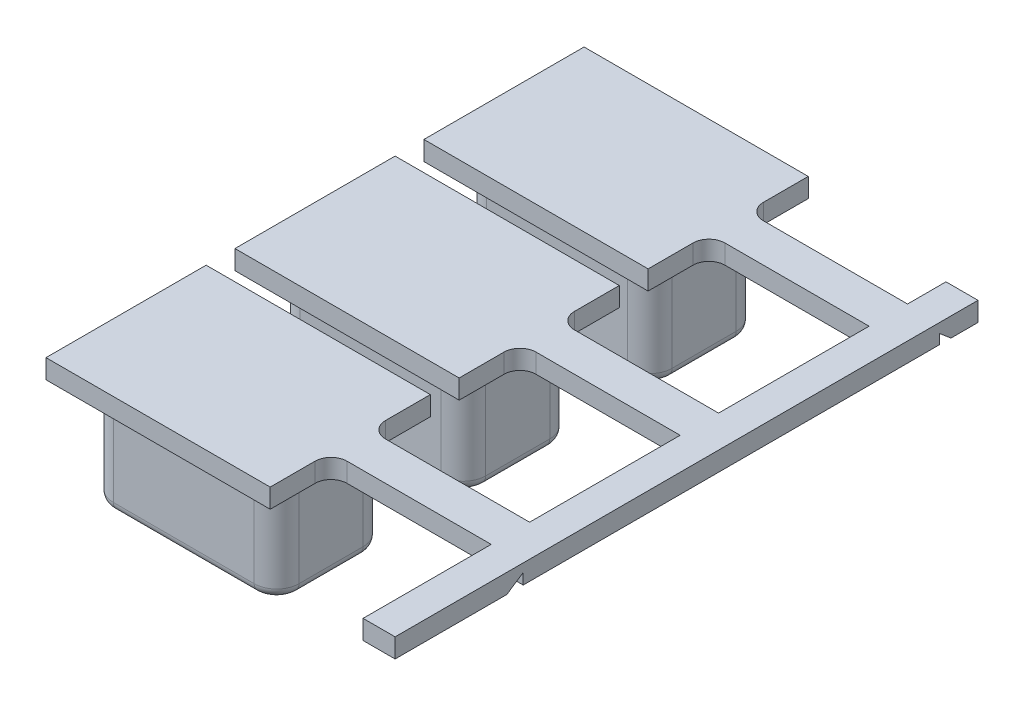
SolidWorks part; units mm, degrees
ref_plane "前视基准面" through (0, 0, 0) normal (0, 0, 1) x (1, 0, 0)
ref_plane "上视基准面" through (0, 0, 0) normal (0, 1, 0) x (1, 0, 0)
ref_plane "右视基准面" through (0, 0, 0) normal (1, 0, 0) x (0, 0, -1)
sketch "草图1" plane through (0, 0, 0) normal (0, 1, 0) x (1, 0, 0)
  line L0 (-2.2, 1.7) -> (2.2, 1.7)
  line L5 (-2.2, 7.5287) -> (2.2, 7.5287)
  line L6 (2.9, 6.8287) -> (2.9, 4.8287)
  line L7 (2.9, 1) -> (2.9, -1)
  line L8 (-2.2, -1.7) -> (2.2, -1.7)
  line L9 (-2.9, 1) -> (-2.9, -1)
  line L10 (-2.2, 4.1287) -> (2.2, 4.1287)
  line L11 (-2.9, 6.8287) -> (-2.9, 4.8287)
  line L12 (-2.2, 13.3491) -> (2.2, 13.3491)
  line L13 (2.9, 12.6491) -> (2.9, 10.6491)
  line L14 (-2.2, 9.9491) -> (2.2, 9.9491)
  line L15 (-2.9, 12.6491) -> (-2.9, 10.6491)
  arc A4 (2.2, 1.7) -> (2.9, 1) centre (2.2, 1) cw
  arc A5 (2.2, -1.7) -> (2.9, -1) centre (2.2, -1) ccw
  arc A6 (-2.9, -1) -> (-2.2, -1.7) centre (-2.2, -1) ccw
  arc A7 (-2.2, 1.7) -> (-2.9, 1) centre (-2.2, 1) ccw
  arc A8 (2.2, 7.5287) -> (2.9, 6.8287) centre (2.2, 6.8287) cw
  arc A9 (2.2, 4.1287) -> (2.9, 4.8287) centre (2.2, 4.8287) ccw
  arc A10 (-2.9, 4.8287) -> (-2.2, 4.1287) centre (-2.2, 4.8287) ccw
  arc A11 (-2.2, 7.5287) -> (-2.9, 6.8287) centre (-2.2, 6.8287) ccw
  arc A12 (2.2, 13.3491) -> (2.9, 12.6491) centre (2.2, 12.6491) cw
  arc A13 (2.2, 9.9491) -> (2.9, 10.6491) centre (2.2, 10.6491) ccw
  arc A14 (-2.9, 10.6491) -> (-2.2, 9.9491) centre (-2.2, 10.6491) ccw
  arc A15 (-2.2, 13.3491) -> (-2.9, 12.6491) centre (-2.2, 12.6491) ccw
  point P0 (0, 0)
  point P1 (-0.0497, 5.8287)
  point P15 (-0.0145, 11.6491)
  dimension "D1" = 3.4
  dimension "D2" = 5.8
extrude "凸台-拉伸1" add sketch "草图1" along normal blind 4
sketch "草图2" plane through (0, 4, 0) normal (0, 1, 0) x (1, 0, 0)
  line L1 (-3.4633, 14.2631) -> (3.5367, 14.2631)
  line L2 (-3.4633, 14.2631) -> (-3.4633, 9.2631)
  line L3 (-3.4633, 9.2631) -> (3.5367, 9.2631)
  line L4 (3.5367, 14.2631) -> (3.5367, 9.2631)
  line L5 (-3.4633, 8.3631) -> (3.5367, 8.3631)
  line L6 (-3.4633, 8.3631) -> (-3.4633, 3.3631)
  line L7 (-3.4633, 3.3631) -> (3.5367, 3.3631)
  line L8 (3.5367, 8.3631) -> (3.5367, 3.3631)
  line L9 (3.5367, 2.4631) -> (-3.4633, 2.4631)
  line L10 (3.5367, 2.4631) -> (3.5367, -2.5369)
  line L11 (3.5367, -2.5369) -> (-3.4633, -2.5369)
  line L12 (-3.4633, 2.4631) -> (-3.4633, -2.5369)
  dimension "D1" = 5
  dimension "D2" = 5
  dimension "D3" = 5
  dimension "D4" = 7
  dimension "D5" = 0.9
  dimension "D6" = 0.9
extrude "凸台-拉伸2" add sketch "草图2" against normal blind 0.6
sketch "草图3" plane through (0, 4, 0) normal (0, 1, 0) x (1, 0, 0)
  line L0 (3.5367, 9.2631) -> (3.5367, 14.2631) construction
  line L1 (3.5367, 12.3631) -> (9.5367, 12.3631)
  line L2 (3.5367, 12.3631) -> (3.5367, 11.1631)
  line L3 (3.5367, 11.1631) -> (9.5367, 11.1631)
  line L4 (9.5367, 12.3631) -> (9.5367, 11.1631)
  line L5 (3.5367, 3.3631) -> (3.5367, 8.3631) construction
  line L6 (3.5367, 6.4631) -> (9.5367, 6.4631)
  line L7 (3.5367, 6.4631) -> (3.5367, 5.2631)
  line L8 (3.5367, 5.2631) -> (9.5367, 5.2631)
  line L9 (9.5367, 6.4631) -> (9.5367, 5.2631)
  line L10 (3.5367, -2.5369) -> (3.5367, 2.4631) construction
  line L11 (3.5367, 0.5631) -> (9.5367, 0.5631)
  line L12 (3.5367, 0.5631) -> (3.5367, -0.6369)
  line L13 (3.5367, -0.6369) -> (9.5367, -0.6369)
  line L14 (9.5367, 0.5631) -> (9.5367, -0.6369)
  line L15 (-3.4633, 14.2631) -> (-3.4633, 9.2631) construction
  line L16 (-3.4633, 8.3631) -> (-3.4633, 3.3631) construction
  line L17 (-3.4633, 2.4631) -> (-3.4633, -2.5369) construction
  point P20 (-3.4633, 11.7631)
  point P21 (9.5367, 11.7631)
  point P24 (-3.4633, 5.8631)
  point P25 (9.5367, 5.8631)
  point P28 (-3.4633, -0.0369)
  point P29 (9.5367, -0.0369)
  dimension "D3" = 1.2
  dimension "D4" = 6
extrude "凸台-拉伸3" add sketch "草图3" against normal blind 0.6
sketch "草图4" plane through (0, 3.4, 0) normal (0, -1, 0) x (1, 0, 0)
  line L0 (3.5367, 0.6369) -> (9.5367, 0.6369) construction
  line L1 (9.5367, 0.6369) -> (8.5367, 0.6369)
  line L2 (9.5367, 0.6369) -> (9.5367, -12.3631)
  line L3 (9.5367, -12.3631) -> (8.5367, -12.3631)
  line L4 (8.5367, 0.6369) -> (8.5367, -12.3631)
  line L5 (9.5367, -12.3631) -> (3.5367, -12.3631) construction
  dimension "D1" = 1
extrude "凸台-拉伸4" add sketch "草图4" against normal blind 0.6
fillet "圆角1" radius 0.5 6 edges at (3.5367, 3.7, -12.3631) (3.5367, 3.7, -11.1631) (3.5367, 3.7, -5.2631) (3.5367, 3.7, -6.4631) (3.5367, 3.7, 0.6369) (3.5367, 3.7, -0.5631)
sketch "草图5" plane through (0, 0, -12.3631) normal (0, 0, -1) x (-1, 0, 0)
  line L0 (-4.0367, 4) -> (-9.5367, 4) construction
  line L1 (-9.5367, 3.4) -> (-8.5367, 3.4)
  line L2 (-9.5367, 3.4) -> (-9.5367, 4)
  line L3 (-9.5367, 4) -> (-8.5367, 4)
  line L4 (-8.5367, 3.4) -> (-8.5367, 4)
  dimension "D1" = 1
  dimension "D2" = 0.6
extrude "凸台-拉伸5" add sketch "草图5" along normal blind 1.2
sketch "草图6" plane through (8.5367, 0, 0) normal (-1, 0, 0) x (0, 0, 1)
  line L0 (-12.3631, 3.4) -> (-12.3631, 3.7)
  line L1 (-12.3631, 3.4) -> (-12.3631, 4) construction
  line L2 (-12.3631, 3.7) -> (-12.7202, 3.4)
  line L3 (-13.5631, 3.4) -> (-12.3631, 3.4) construction
  line L4 (-12.7202, 3.4) -> (-12.3631, 3.4)
extrude "切除-拉伸1" cut sketch "草图6" against normal blind 1
fillet "圆角2" radius 0.3 24 edges at (2.695, 0, -13.1441) (2.9, 0, -11.6491) (2.695, 0, -10.1542) (0, 0, -9.9491) (-2.695, 0, -10.1542) (-2.9, 0, -11.6491) (-2.695, 0, -13.1441) (2.695, 0, -7.3237) (2.9, 0, -5.8287) (2.695, 0, -4.3337) (0, 0, -4.1287) (-2.695, 0, -4.3337) (-2.9, 0, -5.8287) (-2.695, 0, -7.3237) (2.695, 0, -1.495) (2.9, 0, 0) (2.695, 0, 1.495) (0, 0, 1.7) (-2.695, 0, 1.495) (-2.9, 0, 0) (-2.695, 0, -1.495) (0, 0, -13.3491) (0, 0, -7.5287) (0, 0, -1.7)
sketch "草图7" plane through (0, 0, 0.6369) normal (0, 0, 1) x (1, 0, 0)
  line L0 (4.0367, 4) -> (9.5367, 4) construction
  line L1 (9.5367, 3.4) -> (8.5367, 3.4)
  line L2 (9.5367, 3.4) -> (9.5367, 4)
  line L3 (9.5367, 4) -> (8.5367, 4)
  line L4 (8.5367, 3.4) -> (8.5367, 4)
  point P7 (0, 0)
extrude "凸台-拉伸6" add sketch "草图7" along normal blind 4
sketch "草图8" plane through (9.5367, 0, 0) normal (1, 0, 0) x (0, 0, -1)
  line L0 (-0.6369, 3.4) -> (-0.6369, 3.7391)
  line L1 (-4.6369, 3.4) -> (12.3631, 3.4) construction
  line L2 (-0.6369, 3.7391) -> (-1.1492, 3.4)
  line L3 (-1.1492, 3.4) -> (-0.6369, 3.4)
  point P4 (0, 0)
extrude "切除-拉伸2" cut sketch "草图8" against normal blind 2
